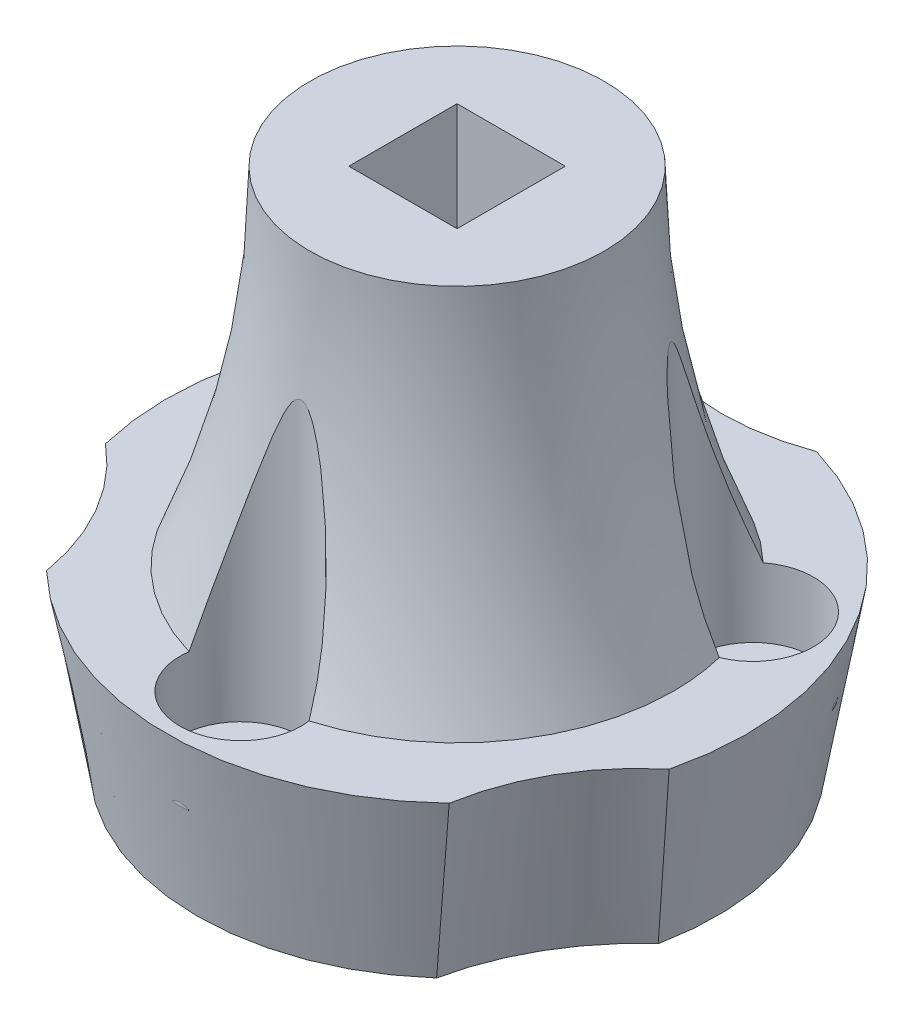
SolidWorks part; units mm, degrees
ref_plane "Front Plane" through (0, 0, 0) normal (0, 0, 1) x (1, 0, 0)
ref_plane "Top Plane" through (0, 0, 0) normal (0, 1, 0) x (1, 0, 0)
ref_plane "Right Plane" through (0, 0, 0) normal (1, 0, 0) x (0, 0, -1)
sketch "Sketch1" plane through (0, 0, 0) normal (0, 1, 0) x (1, 0, 0)
  line L0 (-8.051, 6.858) -> (9.6761, 6.858) construction
  line L1 (0, -12.8344) -> (0, 4.2232) construction
  line L2 (0, 0) -> (0, 14.478) construction
  line L3 (0, 0) -> (12.5383, -7.239) construction
  arc A0 (7.4588, -1.5589) -> (2.3793, 7.239) centre (0, 0) ccw
  arc A1 (-2.3793, 7.239) -> (2.3793, 7.239) centre (0, 14.478) ccw
  arc A2 (7.4588, -1.5589) -> (5.0795, -5.6801) centre (12.5383, -7.239) ccw
  arc A3 (-5.0795, -5.6801) -> (-7.4588, -1.5589) centre (-12.5383, -7.239) ccw
  arc A4 (-5.0795, -5.6801) -> (5.0795, -5.6801) centre (0, 0) ccw
  arc A5 (-2.3793, 7.239) -> (-7.4588, -1.5589) centre (0, 0) ccw
  dimension "D1" = 15.24
  dimension "D3" = 15.24
  dimension "D6" = 25.0766
  dimension "D7" = 14.478
  dimension "D2" = 6.858
  dimension "D4" = 3
  dimension "D5" = 120
extrude "Boss-Extrude1" add sketch "Sketch1" along normal blind 5.08 draft 10 draft outward yes
sketch "Sketch2" plane through (0, 5.08, 0) normal (0, 1, 0) x (1, 0, 0)
  line L0 (0, 0) -> (0, -15.3129) construction
  line L1 (0, 0.0555) -> (-1.3897, 0.0555) construction
  circle A0 centre (0, -6.35) radius 1.016
  arc A1 (-5.9052, -6.1357) -> (5.9052, -6.1357) centre (0, 0) ccw construction
  circle A2 centre (-5.4993, 3.175) radius 1.016
  circle A3 centre (5.4993, 3.175) radius 1.016
  arc A4 (8.2662, -2.0462) -> (2.3611, 8.1819) centre (0, 0) ccw construction
  point P14 (0, 0)
  dimension "D1" = 2.032
  dimension "D2" = 6.35
  dimension "D5" = 5.4993
  dimension "D3" = 3
  dimension "D4" = 10.9985
  dimension "D6" = 3.1195
  dimension "D7" = 6.35
extrude "Cut-Extrude1" cut sketch "Sketch2" against normal through all
sketch "Sketch3" plane through (0, 5.08, 0) normal (0, 1, 0) x (1, 0, 0)
  circle A0 centre (0, -6.35) radius 1.778
  circle A1 centre (-5.4993, 3.175) radius 1.778
  circle A2 centre (5.4993, 3.175) radius 1.778
  arc A3 (8.2662, -2.0462) -> (2.3611, 8.1819) centre (0, 0) ccw construction
  point P10 (0, 0)
  dimension "D1" = 3.556
  dimension "D4" = 6.35
  dimension "D3" = 6.35
  dimension "D2" = 3
extrude "Cut-Extrude2" cut sketch "Sketch3" against normal blind 2.032
sketch "Sketch4" plane through (0, 0, 0) normal (0, -1, 0) x (1, 0, 0)
  circle A0 centre (0, 0) radius 4.3815
  dimension "D1" = 8.763
extrude "Cut-Extrude3" cut sketch "Sketch4" against normal blind 2.032
sketch "Sketch5" plane through (0, 5.08, 0) normal (0, 1, 0) x (1, 0, 0)
  circle A0 centre (0, 0) radius 6.35 construction
  arc A1 (-2.3611, 8.1819) -> (-8.2662, -2.0462) centre (0, 0) ccw construction
  dimension "D1" = 12.7
  dimension "D2" = 0
sketch "Sketch6" plane through (0, 0, 0) normal (0, 0, 1) x (1, 0, 0)
  line L0 (0, 5.08) -> (0, 15.24)
  line L1 (0, 15.24) -> (4.318, 15.24)
  line L2 (6.35, 5.08) -> (-6.35, 5.08) construction
  line L3 (0, 5.08) -> (6.35, 5.08)
  arc A0 (4.318, 15.24) -> (6.35, 5.08) centre (30.734, 15.24) ccw
  dimension "D1" = 10.16
  dimension "D3" = 26.416
  dimension "D2" = 4.318
revolve "Revolve1" add sketch "Sketch6" angle 360 about L0
extrude "Cut-Extrude4" cut sketch "Sketch3<2>" against normal blind 2.032 and the other way blind 10.16
sketch "Sketch3<2>" plane through (0, 5.08, 0) normal (0, 1, 0) x (1, 0, 0) same geometry as "Sketch3"
sketch "Sketch7" plane through (0, 15.24, 0) normal (0, 1, 0) x (1, 0, 0)
  line L1 (1.5875, 1.5875) -> (-1.5875, 1.5875)
  line L2 (1.5875, 1.5875) -> (1.5875, -1.5875)
  line L3 (1.5875, -1.5875) -> (-1.5875, -1.5875)
  line L4 (-1.5875, 1.5875) -> (-1.5875, -1.5875)
  line L5 (1.5875, 1.5875) -> (-1.5875, -1.5875) construction
  line L6 (1.5875, -1.5875) -> (-1.5875, 1.5875) construction
  point P0 (0, 0)
  dimension "D1" = 3.175
  dimension "D2" = 3.175
extrude "Cut-Extrude5" cut sketch "Sketch7" against normal blind 11.43
